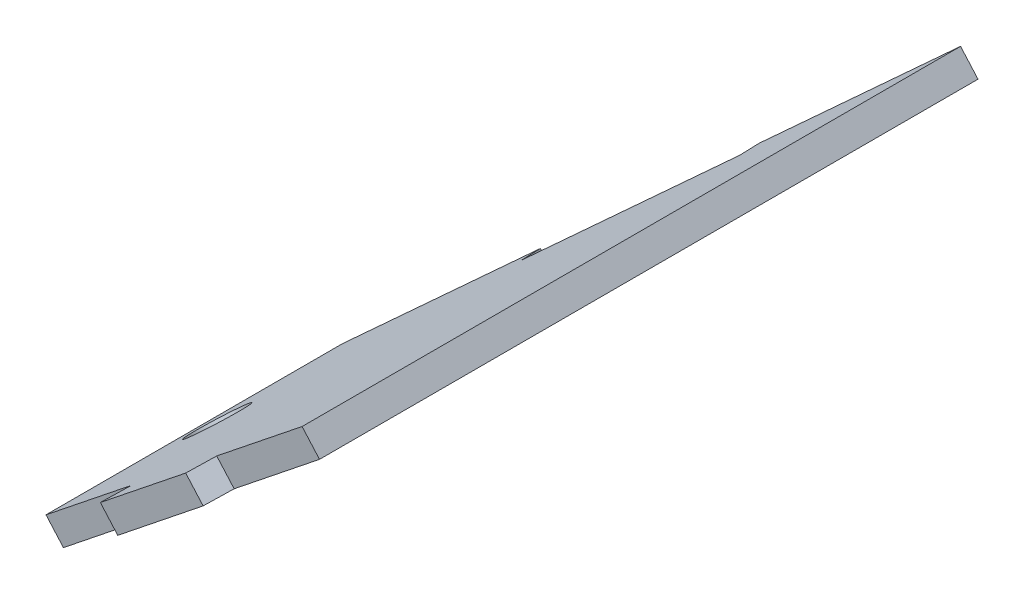
SolidWorks part; units mm, degrees
ref_plane "Front" through (0, 0, 0) normal (0, 0, 1) x (1, 0, 0)
ref_plane "Top" through (0, 0, 0) normal (0, 1, 0) x (1, 0, 0)
ref_plane "Right" through (0, 0, 0) normal (1, 0, 0) x (0, 0, -1)
sketch "Sketch1" plane through (0, 0, 0) normal (0, 1, 0) x (1, 0, 0)
  line L1 (-9, 21.7279) -> (-21.7279, 9)
  line L2 (-21.7279, 9) -> (-21.7279, -9)
  line L3 (-21.7279, -9) -> (-9, -21.7279)
  line L4 (-9, -21.7279) -> (9, -21.7279)
  line L5 (9, -21.7279) -> (21.7279, -9)
  line L6 (21.7279, -9) -> (21.7279, 9)
  line L7 (21.7279, 9) -> (9, 21.7279)
  line L8 (9, 21.7279) -> (-9, 21.7279)
  line L9 (16, -16) -> (-16, -16)
  line L10 (16, -16) -> (16, 16)
  line L11 (16, 16) -> (-16, 16)
  line L12 (-16, -16) -> (-16, 16)
  line L13 (16, -16) -> (-16, 16) construction
  line L14 (16, 16) -> (-16, -16) construction
  circle A0 centre (0, 0) radius 21.7279 construction
  dimension "D1" = 18
  dimension "D2" = 32
sketch "Sketch3" plane through (0, 0, 0) normal (0, 0, 1) x (1, 0, 0)
  line L0 (21.7279, 0) -> (50, 23.4231) construction
  line L3 (50, 23.4231) -> (50, 0) construction
  line L4 (50, 0) -> (21.7279, 0) construction
  line L5 (35.864, 11.7115) -> (0, 55) construction
  line L6 (0, 55) -> (0, 0) construction
  dimension "D1" = 50
  dimension "D2" = 55
ref_plane "Plane1" through (0, 23.4231, 0) normal (0, 1, 0) x (1, 0, 0)
sketch "Sketch4" plane through (0, 23.4231, 0) normal (0, 1, 0) x (1, 0, 0)
  line L1 (48.2843, 20) -> (20, 48.2843)
  line L2 (20, 48.2843) -> (-20, 48.2843)
  line L3 (-20, 48.2843) -> (-48.2843, 20)
  line L4 (-48.2843, 20) -> (-48.2843, -20)
  line L5 (-48.2843, -20) -> (-20, -48.2843)
  line L6 (-20, -48.2843) -> (20, -48.2843)
  line L7 (20, -48.2843) -> (48.2843, -20)
  line L8 (48.2843, -20) -> (48.2843, 20)
  circle A0 centre (0, 0) radius 48.2843 construction
  dimension "D1" = 40
ref_plane "Plane2" through (9.5071, -10.7789, 0) normal (0.6615, -0.75, 0) x (0, 0, -1)
sketch "Sketch5" plane through (9.5071, -10.7789, 0) normal (0.6615, -0.75, 0) x (0, 0, -1)
  line L0 (9, 16.2952) -> (20, 51.7053) construction
  line L1 (20, 51.7053) -> (-20, 51.7053) construction
  line L2 (-20, 51.7053) -> (-9, 16.2952) construction
  line L3 (-9, 16.2952) -> (9, 16.2952) construction
  line L4 (-18.3246, 51.7053) -> (21.6754, 51.7053)
  line L5 (21.6754, 51.7053) -> (18.0908, 40.166)
  line L6 (18.0166, 39.9273) -> (16.4887, 40.4019) construction
  line L7 (16.4887, 40.4019) -> (12.822, 28.5985) construction
  line L8 (12.822, 28.5985) -> (14.35, 28.1239) construction
  line L9 (14.2016, 27.6464) -> (10.6754, 16.2952)
  line L10 (10.6754, 16.2952) -> (9, 16.2952)
  line L11 (9, 16.2952) -> (-7.3246, 16.2952)
  line L12 (-7.3246, 16.2952) -> (-10.9912, 28.0985)
  line L13 (-10.9912, 28.0985) -> (-12.5192, 27.6239)
  line L14 (-12.5192, 27.6239) -> (-16.1859, 39.4273)
  line L15 (-16.1859, 39.4273) -> (-14.6579, 39.9019)
  line L16 (-14.6579, 39.9019) -> (-18.3246, 51.7053)
  line L17 (12.822, 28.5985) -> (-10.9912, 28.0985) construction
  line L18 (16.4887, 40.4019) -> (-14.6579, 39.9019) construction
  line L19 (0.8377, 16.2952) -> (0.8377, 19.2952) construction
  line L20 (18.0908, 40.166) -> (16.5628, 40.6407)
  line L21 (16.5628, 40.6407) -> (12.6737, 28.1211)
  line L22 (12.6737, 28.1211) -> (14.2016, 27.6464)
  line L23 (18.0908, 40.166) -> (18.0166, 39.9273) construction
  line L24 (14.35, 28.1239) -> (14.2016, 27.6464) construction
  circle A0 centre (0.8377, 19.2952) radius 3 construction
  dimension "D2" = 6
  dimension "D1" = 1.6
  dimension "D3" = 0.5
  dimension "D4" = 0.5
  dimension "D5" = 0.25
extrude "Boss-Extrude1" add sketch "Sketch5" along normal blind 1.6
hole_wizard "M3 Clearance Hole1" positions "Sketch7" profile "Sketch6" hole size "M3" standard "ISO" end condition through all
sketch "Sketch7" plane through (9.5071, -10.7789, 0) normal (-0.6615, 0.75, 0) x (0.75, 0.6615, 0)
  point P0 (19.2952, 0.8377)
sketch "Sketch6" plane through (23.9778, 1.9844, -0.8377) normal (0, 0, 1) x (-0.75, -0.6615, 0)
  line L0 (0, 0) -> (0, 19.1665)
  line L1 (0, 19.1665) -> (1.7, 19.1665)
  line L2 (1.7, 19.1665) -> (1.7, 0)
  line L5 (1.7, 0) -> (0, 0)
  line L11 (0, -6.35) -> (0, 107.95) construction
  dimension "Thru Hole Dia." = 3.4
  dimension "Thru Hole Depth" = 19.1665
ref_plane "Plane3" through (10.0363, -11.3789, 0) normal (0.6615, -0.75, 0) x (0, 0, -1)
ref_plane "Plane4" through (-0.6587, -0.581, 2.8274) normal (-0.2225, -0.1962, 0.955) x (0.9749, -0.0448, 0.2179)
ref_axis "Axis1" through (52.3872, 25.9752, 20.6426) along (-0.7162, -0.6317, -0.2967)
ref_plane "Plane5" through (-1.0147, -0.895, -4.3554) normal (-0.2225, -0.1962, -0.955) x (-0.9749, 0.0448, 0.2179)
ref_axis "Axis2" through (19.3348, -3.1775, -8.6272) along (0.7162, 0.6317, -0.2967)
